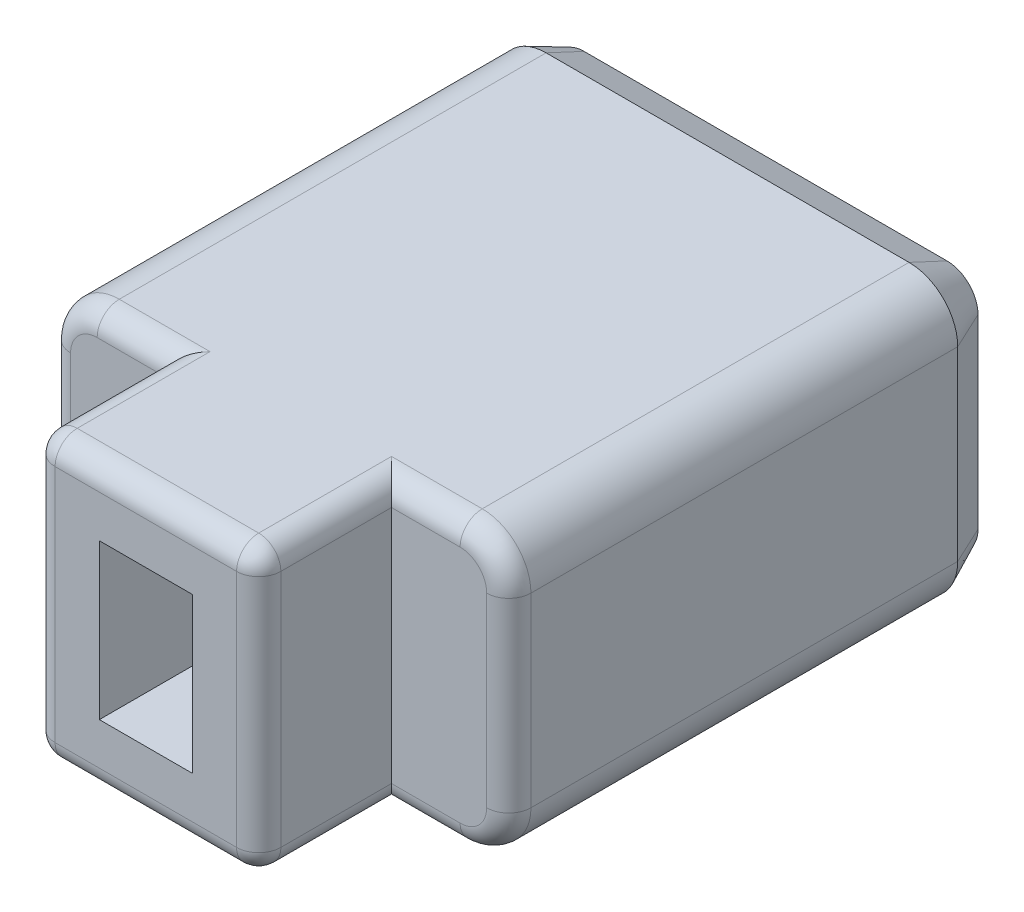
SolidWorks part; units mm, degrees
ref_plane "Plan de face" through (0, 0, 0) normal (0, 0, 1) x (1, 0, 0)
ref_plane "Plan de dessus" through (0, 0, 0) normal (0, 1, 0) x (1, 0, 0)
ref_plane "Plan de droite" through (0, 0, 0) normal (1, 0, 0) x (0, 0, -1)
sketch "Esquisse2" plane through (0, 0, 0) normal (0, 0, 1) x (1, 0, 0)
  line L1 (1.1, 0) -> (9.3, 0)
  line L2 (0, 1.1) -> (0, 5.3)
  line L3 (1.1, 6.4) -> (9.3, 6.4)
  line L4 (10.4, 1.1) -> (10.4, 5.3)
  arc A0 (9.3, 6.4) -> (10.4, 5.3) centre (9.3, 5.3) cw
  arc A1 (9.3, 0) -> (10.4, 1.1) centre (9.3, 1.1) ccw
  arc A2 (1.1, 0) -> (0, 1.1) centre (1.1, 1.1) cw
  arc A3 (0, 5.3) -> (1.1, 6.4) centre (1.1, 5.3) cw
  point P7 (10.4, 6.4)
  point P12 (0, 0)
  point P15 (0, 6.4)
  dimension "D3" = 1.1
  dimension "D1" = 10.4
  dimension "D2" = 6.4
extrude "Boss.-Extru.1" add sketch "Esquisse2" along normal blind 14
sketch "Esquisse3" plane through (0, 0, 14) normal (0, 0, 1) x (1, 0, 0)
  line L0 (0, 5.3) -> (0, 1.1) construction
  line L1 (4.15, 4.95) -> (6.25, 4.95)
  line L2 (4.15, 4.95) -> (4.15, 1.45)
  line L3 (4.15, 1.45) -> (6.25, 1.45)
  line L4 (6.25, 4.95) -> (6.25, 1.45)
  line L5 (10.4, 1.1) -> (10.4, 5.3) construction
  line L6 (9.3, 6.4) -> (1.1, 6.4) construction
  line L7 (1.1, 0) -> (9.3, 0) construction
  dimension "D1" = 2.1
  dimension "D2" = 3.5
  dimension "D3" = 4.15
  dimension "D4" = 4.15
  dimension "D5" = 1.45
  dimension "D6" = 1.45
extrude "Enlèv. mat.-Extru.1" cut sketch "Esquisse3" against normal blind 3
sketch "Esquisse4" plane through (0, 0, 14) normal (0, 0, 1) x (1, 0, 0)
  line L0 (2.65, 6.4) -> (2.65, 0)
  line L1 (9.3, 6.4) -> (1.1, 6.4) construction
  line L2 (1.1, 0) -> (9.3, 0) construction
  line L3 (2.65, 0) -> (7.75, 0)
  line L4 (7.75, 0) -> (7.75, 6.4)
  line L5 (7.75, 6.4) -> (2.65, 6.4)
  line L6 (4.15, 4.95) -> (4.15, 1.45) construction
  line L7 (6.25, 1.45) -> (6.25, 4.95) construction
  dimension "D1" = 1.5
  dimension "D2" = 1.5
extrude "Enlèv. mat.-Extru.2" cut sketch "Esquisse4" against normal blind 3 flip side to cut
fillet "Congé1" radius 0.5 18 edges at (8.525, 0, 11) (10.0778, 0.3222, 11) (10.4, 3.2, 11) (10.0778, 6.0778, 11) (1.875, 6.4, 11) (0.3222, 6.0778, 11) (1.875, 0, 11) (0.3222, 0.3222, 11) (7.75, 6.4, 12.5) (2.65, 6.4, 12.5) (7.75, 0, 12.5) (2.65, 0, 12.5) (2.65, 3.2, 14) (5.2, 6.4, 14) (7.75, 3.2, 14) (5.2, 0, 14) (8.525, 6.4, 11) (0, 3.2, 11)
chamfer "Chanfrein1" distance 0.4 angle 65 8 edges at (5.2, 0, 0) (10.0778, 0.3222, 0) (0.3222, 0.3222, 0) (10.4, 3.2, 0) (0, 3.2, 0) (10.0778, 6.0778, 0) (0.3222, 6.0778, 0) (5.2, 6.4, 0) first distance on face at (5.2, 3.2, 0)
sketch "Esquisse5" plane through (0, 0, 0) normal (0, 0, -1) x (-1, 0, 0)
  line L0 (-0.4, 5.3) -> (-10, 5.3) construction
  arc A0 (-9.3, 6) -> (-10, 5.3) centre (-9.3, 5.3) ccw construction
  text T0 "5" font "Century Gothic" height 4
extrude "Enlèv. mat.-Extru.3" cut sketch "Esquisse5" against normal blind 0.3
extrude "Boss.-Extru.2" add sketch "Esquisse5<2>" along normal blind 0.3 separate body
sketch "Esquisse5<2>" plane through (0, 0, 0) normal (0, 0, -1) x (-1, 0, 0) same geometry as "Esquisse5"
